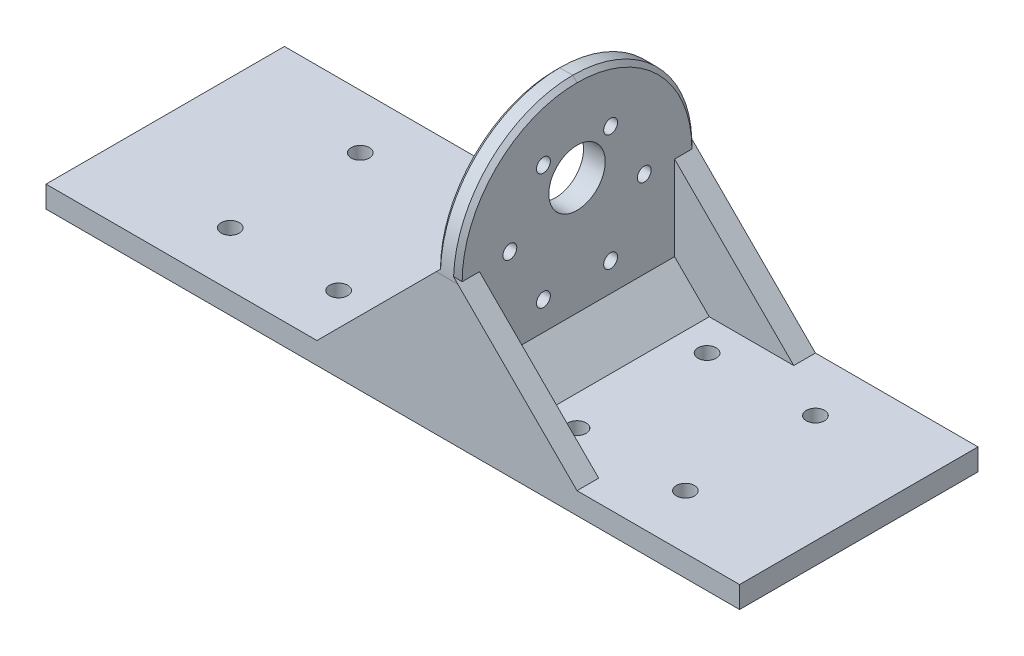
SolidWorks part; units mm, degrees
material "ABS"
ref_plane "前视基准面" through (0, 0, 0) normal (0, 0, 1) x (1, 0, 0)
ref_plane "上视基准面" through (0, 0, 0) normal (0, 1, 0) x (1, 0, 0)
ref_plane "右视基准面" through (0, 0, 0) normal (1, 0, 0) x (0, 0, -1)
sketch "草图1" plane through (0, 0, 0) normal (0, 1, 0) x (1, 0, 0)
  line L1 (-80, 27.5) -> (80, 27.5)
  line L2 (-80, 27.5) -> (-80, -27.5)
  line L3 (-80, -27.5) -> (80, -27.5)
  line L4 (80, 27.5) -> (80, -27.5)
  line L5 (-80, 27.5) -> (80, -27.5) construction
  line L6 (-80, -27.5) -> (80, 27.5) construction
  point P0 (0, 0)
extrude "凸台-拉伸1" add sketch "草图1" along normal blind 5
sketch "草图2" plane through (0, 5, 0) normal (0, 1, 0) x (1, 0, 0)
  line L0 (-80, 0) -> (10, 0) construction
  line L3 (-80, 27.5) -> (-80, -27.5) construction
  line L4 (10, 0) -> (10, 27.5)
  line L5 (80, 27.5) -> (-80, 27.5) construction
  line L6 (10, 27.5) -> (15, 27.5)
  line L7 (15, 27.5) -> (15, -27.5)
  line L8 (-80, -27.5) -> (80, -27.5) construction
  line L9 (15, -27.5) -> (10, -27.5)
  line L10 (10, -27.5) -> (10, 0)
  dimension "D1" = 90
extrude "凸台-拉伸2" add sketch "草图2" along normal blind 55
fillet "圆角1" radius 27.5 2 edges at (12.5, 60, -27.5) (12.5, 60, 27.5)
sketch "草图3" plane through (10, 0, 0) normal (-1, 0, 0) x (0, 0, 1)
  line L0 (0, 60) -> (0, 40) construction
  circle A0 centre (0, 40) radius 6.5
  dimension "D1" = 20
extrude "切除-拉伸1" cut sketch "草图3" against normal up to next
sketch "草图4" plane through (10, 0, 0) normal (-1, 0, 0) x (0, 0, 1)
  line L0 (0, 5) -> (0, 33) construction
  line L1 (-27.5, 5) -> (27.5, 5) construction
  circle A0 centre (0, 33) radius 15.5 construction
  circle A1 centre (15.5, 33) radius 1.6
  circle A2 centre (7.75, 19.5766) radius 1.6
  circle A3 centre (-7.75, 19.5766) radius 1.6
  circle A4 centre (-15.5, 33) radius 1.6
  circle A5 centre (-7.75, 46.4234) radius 1.6
  circle A6 centre (7.75, 46.4234) radius 1.6
  point P21 (0, 33)
  dimension "D2" = 6
  dimension "D1" = 28
extrude "切除-拉伸2" cut sketch "草图4" against normal blind 10
chamfer "倒角1" distance 8 angle 45 1 edges at (10, 5, 0)
chamfer "倒角2" distance 8 angle 45 1 edges at (15, 5, 0)
sketch "草图6" plane through (0, 0, 27.5) normal (0, 0, 1) x (1, 0, 0)
  line L0 (0, 0) -> (0, 5) construction
  line L1 (-80, 5) -> (2, 5) construction
  line L2 (0, 5) -> (10, 5) construction
  line L3 (10, 5) -> (10, 32.5)
  line L4 (10, 32.5) -> (10, 13) construction
  line L5 (10, 5) -> (-17.5, 5)
  line L6 (-17.5, 5) -> (10, 32.5)
  line L7 (10, 32.5) -> (15, 32.5) construction
  line L8 (15, 32.5) -> (15, 5)
  line L9 (15, 5) -> (42.5, 5)
  line L10 (23, 5) -> (80, 5) construction
  line L11 (42.5, 5) -> (15, 32.5)
extrude "凸台-拉伸5" add sketch "草图6" against normal blind 5
mirror "镜向1" about plane through (0, 0, 0) normal (0, 0, 1) of "凸台-拉伸5"
chamfer "倒角3" distance 1 angle 45 4 edges at (15, 51.9454, -19.4454) (15, 51.9454, 19.4454) (10, 51.9454, 19.4454) (10, 51.9454, -19.4454)
sketch "草图7" plane through (0, 0, 0) normal (0, -1, 0) x (-1, 0, 0)
  line L0 (80, 0) -> (50, 0) construction
  line L1 (80, 27.5) -> (80, -27.5) construction
  line L2 (50, 0) -> (50, -15) construction
  line L3 (50, -15) -> (25, -15) construction
  line L4 (25, -15) -> (-30, -15) construction
  line L5 (-30, -15) -> (-55, -15) construction
  circle A0 centre (50, -15) radius 2.1
  circle A1 centre (25, -15) radius 2.1
  circle A2 centre (-30, -15) radius 2.1
  circle A3 centre (-55, -15) radius 2.1
  circle A4 centre (-55, 15) radius 2.1
  circle A5 centre (-30, 15) radius 2.1
  circle A6 centre (25, 15) radius 2.1
  circle A7 centre (50, 15) radius 2.1
extrude "切除-拉伸3" cut sketch "草图7" against normal blind 5
